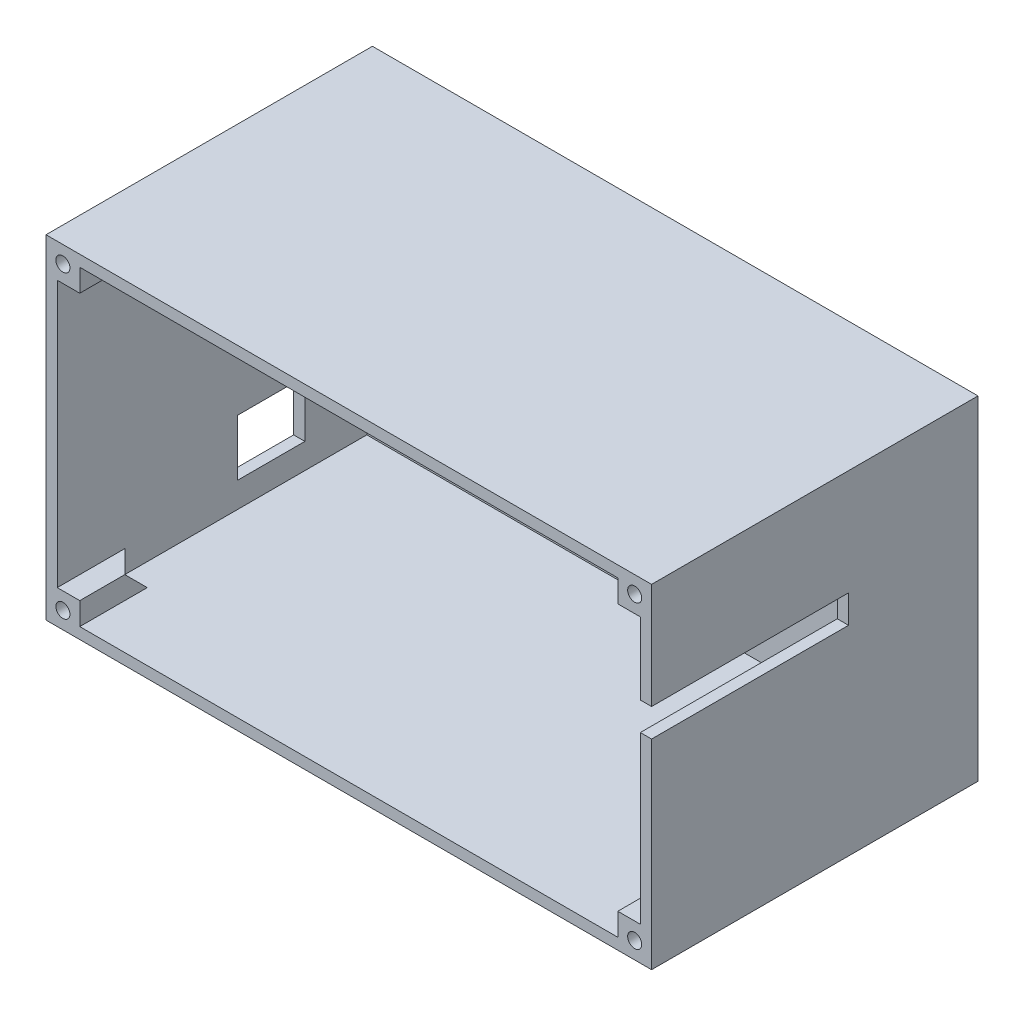
SolidWorks part; units mm, degrees
ref_plane "Front Plane" through (0, 0, 0) normal (0, 0, 1) x (1, 0, 0)
ref_plane "Top Plane" through (0, 0, 0) normal (0, 1, 0) x (1, 0, 0)
ref_plane "Right Plane" through (0, 0, 0) normal (1, 0, 0) x (0, 0, -1)
sketch "Sketch1" plane through (0, 0, 0) normal (0, 0, 1) x (1, 0, 0)
  line L1 (0, 0) -> (107.6, 0)
  line L2 (0, 0) -> (0, 59.3)
  line L3 (0, 59.3) -> (107.6, 59.3)
  line L4 (107.6, 0) -> (107.6, 59.3)
  line L5 (2, 2) -> (105.6, 2)
  line L6 (2, 2) -> (2, 57.3)
  line L7 (2, 57.3) -> (105.6, 57.3)
  line L8 (105.6, 2) -> (105.6, 57.3)
  dimension "D1" = 107.6
  dimension "D2" = 59.3
  dimension "D3" = 2
  dimension "D4" = 2
  dimension "D5" = 2
  dimension "D6" = 2
extrude "Boss-Extrude1" add sketch "Sketch1" along normal blind 55
sketch "Sketch2" plane through (0, 0, 0) normal (0, 0, -1) x (-1, 0, 0)
  line L1 (-107.6, 59.3) -> (0, 59.3)
  line L2 (-107.6, 59.3) -> (-107.6, 0)
  line L3 (-107.6, 0) -> (0, 0)
  line L4 (0, 59.3) -> (0, 0)
  circle A0 centre (-18.3, 53.7) radius 1.5
  circle A1 centre (-17, 5.5) radius 1.5
  circle A2 centre (-93.2, 53.7) radius 1.5
  circle A3 centre (-99.5, 5.5) radius 1.5
  dimension "D1" = 3
  dimension "D2" = 3
  dimension "D3" = 3
  dimension "D4" = 3
  dimension "D5" = 1.3
  dimension "D6" = 53.7
  dimension "D7" = 17
  dimension "D8" = 5.5
  dimension "D9" = 5.5
  dimension "D10" = 74.9
  dimension "D11" = 5.6
  dimension "D12" = 99.5
extrude "Boss-Extrude2" add sketch "Sketch2" along normal blind 3
sketch "Sketch3" plane through (0, 0, -3) normal (0, 0, -1) x (-1, 0, 0)
  circle A0 centre (-93.2, 53.7) radius 2.5
  circle A1 centre (-18.3, 53.7) radius 2.5
  circle A2 centre (-17, 5.5) radius 2.5
  circle A3 centre (-99.5, 5.5) radius 2.5
  dimension "D1" = 5
  dimension "D2" = 5
  dimension "D3" = 5
  dimension "D4" = 5
extrude "Cut-Extrude1" cut sketch "Sketch3" against normal blind 1.5
sketch "Sketch4" plane through (0, 0, 0) normal (-1, 0, 0) x (0, 0, 1)
  line L0 (-3, 0) -> (-3, 59.3) construction
  line L1 (11, 16.5) -> (23, 16.5)
  line L2 (11, 16.5) -> (11, 6.5)
  line L3 (11, 6.5) -> (23, 6.5)
  line L4 (23, 16.5) -> (23, 6.5)
  line L5 (55, 0) -> (-3, 0) construction
  dimension "D1" = 14
  dimension "D2" = 6.5
  dimension "D3" = 12
  dimension "D4" = 10
extrude "Cut-Extrude2" cut sketch "Sketch4" against normal blind 5
sketch "Sketch5" plane through (107.6, 0, 0) normal (1, 0, 0) x (0, 0, -1)
  line L0 (-55, 0) -> (-55, 59.3) construction
  line L1 (-55, 40.5) -> (-20, 40.5)
  line L2 (-55, 40.5) -> (-55, 35.5)
  line L3 (-55, 35.5) -> (-20, 35.5)
  line L4 (-20, 40.5) -> (-20, 35.5)
  line L5 (-55, 0) -> (3, 0) construction
  line L6 (3, 59.3) -> (3, 0) construction
  point P8 (-20, 38)
  dimension "D1" = 35.5
  dimension "D2" = 5
  dimension "D3" = 23
extrude "Cut-Extrude3" cut sketch "Sketch5" against normal blind 5
sketch "Sketch7" plane through (0, 0, 0) normal (-1, 0, 0) x (0, 0, 1)
  line L0 (55, 0) -> (-3, 0) construction
  line L1 (-3, 59.3) -> (0, 59.3)
  line L2 (-3, 59.3) -> (-3, 0)
  line L3 (-3, 0) -> (0, 0)
  line L4 (0, 59.3) -> (0, 0)
  dimension "D1" = 3
sketch "Sketch8" plane through (0, 0, 0) normal (0, 0, 1) x (1, 0, 0)
  line L0 (2, 57.3) -> (2, 2) construction
  line L1 (107.6, 59.3) -> (0, 59.3) construction
  circle A0 centre (10, 51.3) radius 1.75
  circle A4 centre (85, 51.3) radius 1.75
  circle A5 centre (85, 7.3) radius 1.75
  circle A6 centre (10, 7.3) radius 1.75
  dimension "D1" = 8
  dimension "D2" = 8
  dimension "D3" = 3.5
  dimension "D4" = 2
  dimension "D5" = 2
extrude "Cut-Extrude4" cut sketch "Sketch8" against normal blind 10
chamfer "Chamfer1" distance 2 angle 45 4 edges at (11.75, 7.3, 0) (86.75, 7.3, 0) (86.75, 51.3, 0) (11.75, 51.3, 0)
sketch "Sketch9" plane through (0, 0, 55) normal (0, 0, 1) x (1, 0, 0)
  line L5 (2, 2) -> (6, 2)
  line L6 (2, 2) -> (2, 6)
  line L7 (2, 6) -> (6, 6)
  line L8 (6, 2) -> (6, 6)
  line L9 (105.6, 57.3) -> (101.6, 57.3)
  line L10 (105.6, 57.3) -> (105.6, 53.3)
  line L11 (105.6, 53.3) -> (101.6, 53.3)
  line L12 (101.6, 57.3) -> (101.6, 53.3)
  line L13 (105.6, 2) -> (101.6, 2)
  line L14 (105.6, 2) -> (105.6, 6)
  line L15 (105.6, 6) -> (101.6, 6)
  line L16 (101.6, 2) -> (101.6, 6)
  line L17 (2, 57.3) -> (6, 57.3)
  line L18 (2, 57.3) -> (2, 53.3)
  line L19 (2, 53.3) -> (6, 53.3)
  line L20 (6, 57.3) -> (6, 53.3)
  dimension "D1" = 4
  dimension "D2" = 4
  dimension "D3" = 4
  dimension "D4" = 4
  dimension "D5" = 4
  dimension "D6" = 4
  dimension "D7" = 4
  dimension "D8" = 4
extrude "Boss-Extrude4" add sketch "Sketch9" against normal blind 8
chamfer "Chamfer2" distance 4 angle 45 8 edges at (4, 57.3, 47) (2, 55.3, 47) (4, 2, 47) (2, 4, 47) (105.6, 4, 47) (103.6, 2, 47) (103.6, 57.3, 47) (105.6, 55.3, 47)
sketch "Sketch10" plane through (0, 0, 55) normal (0, 0, 1) x (1, 0, 0)
  line L1 (107.6, 59.3) -> (0, 59.3) construction
  line L2 (0, 59.3) -> (0, 0) construction
  circle A0 centre (3, 56.3) radius 1.25
  circle A4 centre (104.6, 56.3) radius 1.25
  circle A5 centre (104.6, 3) radius 1.25
  circle A6 centre (3, 3) radius 1.25
  dimension "D1" = 3
  dimension "D2" = 3
  dimension "D3" = 2.5
  dimension "D4" = 2
  dimension "D5" = 2
extrude "Cut-Extrude5" cut sketch "Sketch10" against normal blind 5
